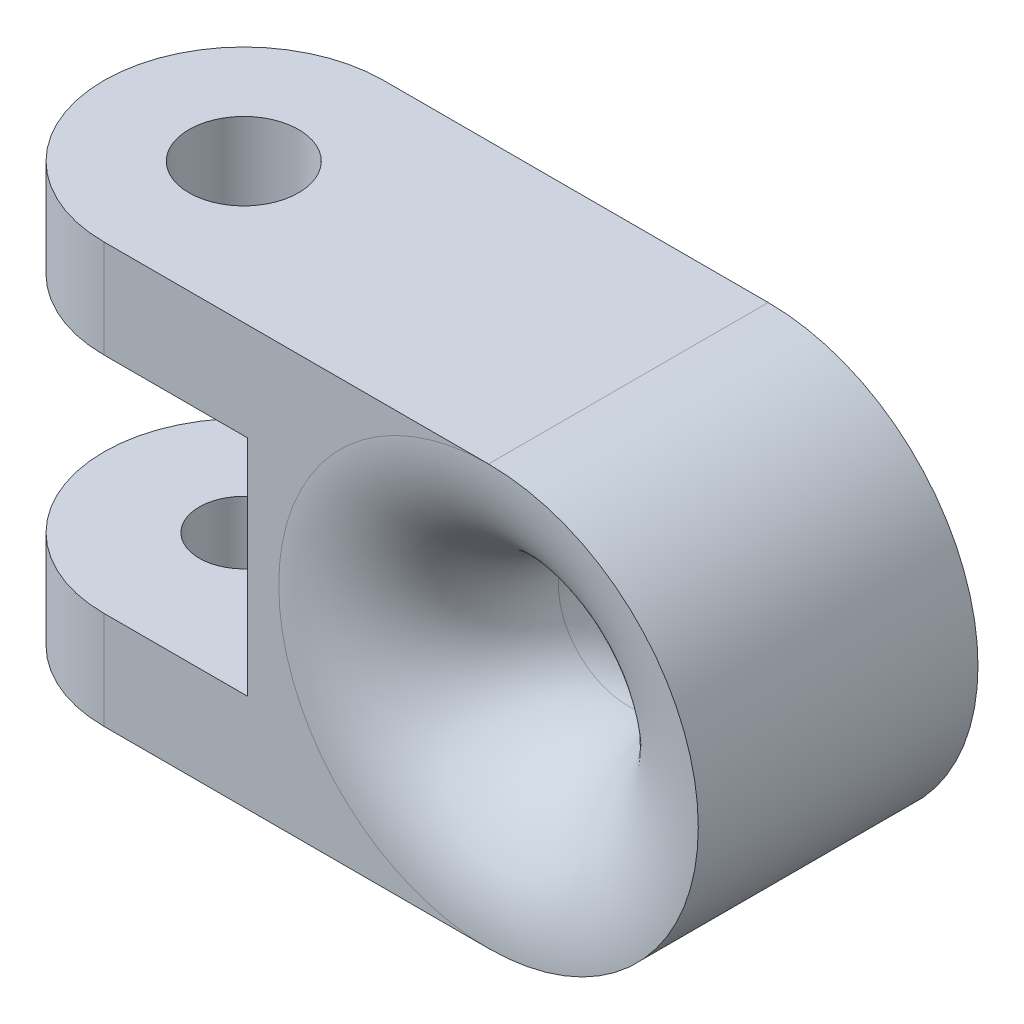
SolidWorks part; units mm, degrees
ref_plane "Front Plane" through (0, 0, 0) normal (0, 0, 1) x (1, 0, 0)
ref_plane "Top Plane" through (0, 0, 0) normal (0, 1, 0) x (1, 0, 0)
ref_plane "Right Plane" through (0, 0, 0) normal (1, 0, 0) x (0, 0, -1)
sketch "Sketch1" plane through (0, 0, 0) normal (0, 1, 0) x (1, 0, 0)
  line L0 (0, 0) -> (-11.1125, 0) construction
  line L1 (0, -6.35) -> (-11.1125, -6.35)
  line L2 (0, 6.35) -> (-11.1125, 6.35)
  line L3 (0, 6.35) -> (0, -6.35)
  arc A1 (-11.1125, 6.35) -> (-11.1125, -6.35) centre (-11.1125, 0) ccw
  point P3 (-5.5562, 0)
  dimension "D2" = 6.35
  dimension "D1" = 11.1125
extrude "Boss-Extrude1" add sketch "Sketch1" along normal mid plane 19.05
sketch "Sketch2" plane through (0, 0, 6.35) normal (0, 0, 1) x (1, 0, 0)
  line L0 (0, 0) -> (6.35, 0) construction
  line L1 (0, 9.525) -> (0, -9.525) construction
  line L2 (0, 9.525) -> (6.35, 9.525)
  line L3 (0, -9.525) -> (6.35, -9.525)
  line L4 (-11.1125, 9.525) -> (0, 9.525) construction
  arc A0 (0, 9.525) -> (0, -9.525) centre (0, 0) ccw
  arc A1 (6.35, -9.525) -> (6.35, 9.525) centre (6.35, 0) ccw
  point P4 (3.175, 0)
  dimension "D1" = 6.35
extrude "Boss-Extrude2" add sketch "Sketch2" against normal up to surface (12.7 mm away) up to face at (-5.5562, 0, -6.35)
sketch "Sketch3" plane through (0, 0, 0) normal (0, 1, 0) x (1, 0, 0)
  line L0 (6.35, 6.35) -> (-11.1125, 6.35) construction
  line L1 (-11.1125, -6.35) -> (6.35, -6.35) construction
  line L2 (-4.589, 6.35) -> (-11.1125, 6.35)
  line L3 (-11.1125, -6.35) -> (-4.589, -6.35)
  line L4 (-4.589, -6.35) -> (-4.589, 6.35)
  arc A0 (-11.1125, 6.35) -> (-11.1125, -6.35) centre (-11.1125, 0) ccw construction
  arc A1 (-11.1125, 6.35) -> (-11.1125, -6.35) centre (-11.1125, 0) ccw
  dimension "D1" = 6.5235
extrude "Cut-Extrude1" cut sketch "Sketch3" against normal mid plane 10.16
hole_wizard "#10-32 Tapped Hole1" positions "Sketch4" profile "Sketch5" tap size "#10-32" standard "ANSI Inch" end condition through all
sketch "Sketch4" plane through (0, -5.08, 0) normal (0, 1, 0) x (1, 0, 0)
  point P0 (-11.1125, 0)
sketch "Sketch5" plane through (-11.1125, -5.08, 0) normal (1, 0, 0) x (0, 0, 1)
  line L0 (0, 0) -> (0, 4.445)
  line L1 (0, 4.445) -> (2.0193, 4.445)
  line L2 (2.0193, 4.445) -> (2.0193, 0)
  line L5 (2.0193, 0) -> (0, 0)
  line L11 (0, -6.35) -> (0, 107.95) construction
  dimension "Thru Tap Drill Dia." = 4.0386
  dimension "Thru Tap Drill Depth" = 4.445
cosmetic thread "Hole Thread1" parameters "D2"=4.826
hole_wizard "#10 Clearance Hole1" positions "Sketch6" profile "Sketch8" hole size "#10" standard "ANSI Inch"
sketch "Sketch6" plane through (0, 9.525, 0) normal (0, 1, 0) x (1, 0, 0)
  point P0 (-11.1125, 0)
sketch "Sketch8" plane through (-11.1125, 9.525, 0) normal (1, 0, 0) x (0, 0, 1)
  line L0 (0, 0) -> (0, 16.0997)
  line L1 (0, 16.0997) -> (2.4892, 14.604)
  line L2 (2.4892, 14.604) -> (2.4892, 0)
  line L5 (2.4892, 0) -> (0, 0)
  line L10 (0, 16.0997) -> (-2.4892, 14.604) construction
  line L11 (0, -6.35) -> (0, 107.95) construction
  dimension "Hole Dia." = 4.9784
  dimension "Hole Depth" = 14.604
  dimension "Drill Angle" = 118
hole_wizard "1/4 (0.25) Diameter Hole1" positions "Sketch9" profile "Sketch10" hole size "1/4" standard "ANSI Inch" end condition through all
sketch "Sketch9" plane through (0, 0, -6.35) normal (0, 0, -1) x (-1, 0, 0)
  point P0 (-6.35, 0)
sketch "Sketch10" plane through (6.35, 0, -6.35) normal (1, 0, 0) x (0, 1, 0)
  line L0 (0, 0) -> (0, 12.7)
  line L1 (0, 12.7) -> (3.175, 12.7)
  line L2 (3.175, 12.7) -> (3.175, 0)
  line L5 (3.175, 0) -> (0, 0)
  line L11 (0, -6.35) -> (0, 107.95) construction
  dimension "Thru Hole Dia." = 6.35
  dimension "Thru Hole Depth" = 12.7
fillet "Fillet1" radius 6.35 2 edges at (3.175, 0, 6.35) (3.175, 0, -6.35)
equation "\"D1@Sketch3\"=.1875+1.38mm+.015"
